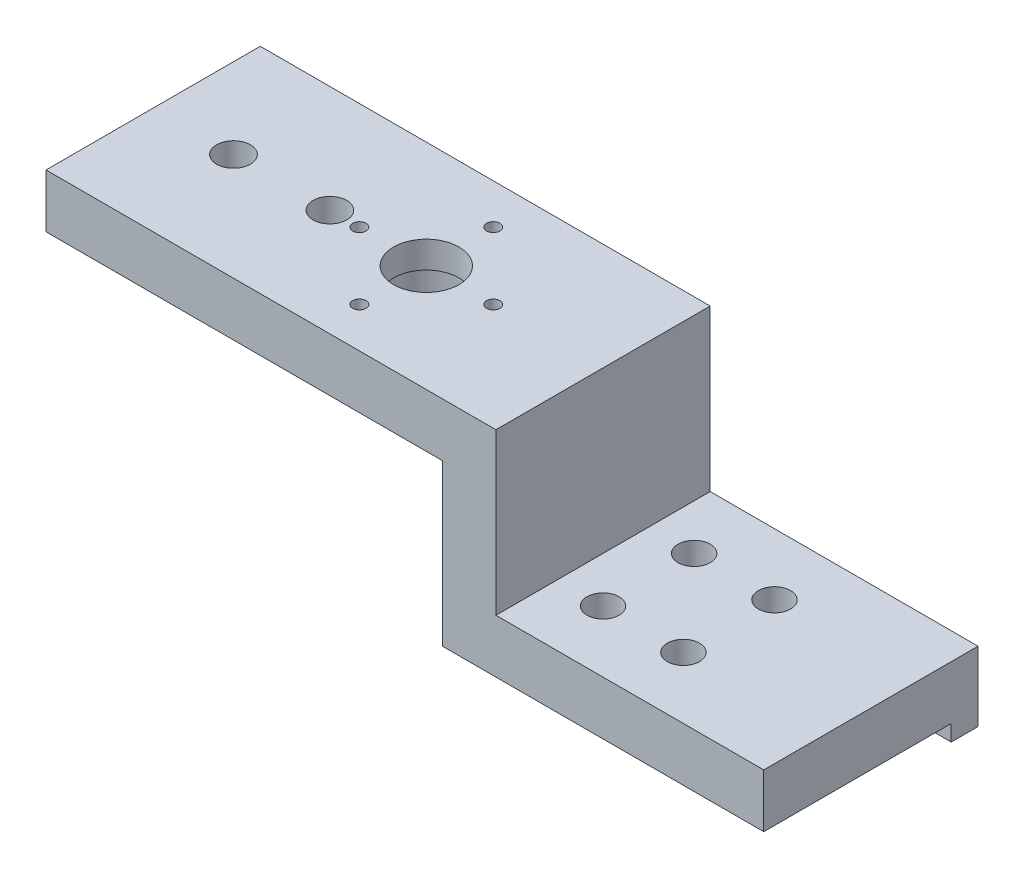
SolidWorks part; units mm, degrees
ref_plane "Front Plane" through (0, 0, 0) normal (0, 0, 1) x (1, 0, 0)
ref_plane "Top Plane" through (0, 0, 0) normal (0, 1, 0) x (1, 0, 0)
ref_plane "Right Plane" through (0, 0, 0) normal (1, 0, 0) x (0, 0, -1)
sketch "Sketch1" plane through (0, 0, 0) normal (0, 1, 0) x (1, 0, 0)
  line L1 (-30, -20) -> (30, -20)
  line L2 (-30, -20) -> (-30, 20)
  line L3 (-30, 20) -> (30, 20)
  line L4 (30, -20) -> (30, 20)
  line L5 (0, 20) -> (0, -20) construction
  line L6 (-30, 0) -> (30, 0) construction
  point P0 (0, 0)
  dimension "D1" = 40
  dimension "D2" = 60
extrude "Boss-Extrude1" add sketch "Sketch1" along normal blind 10 contours L3 L4 L1 L2
sketch "Sketch2" plane through (0, 10, 0) normal (0, 1, 0) x (1, 0, 0)
  line L1 (-20, -20) -> (-30, -20)
  line L2 (-20, -20) -> (-20, 20)
  line L3 (-20, 20) -> (-30, 20)
  line L4 (-30, -20) -> (-30, 20)
  line L5 (-25, 20) -> (-25, -20) construction
  line L6 (-20, 0) -> (-30, 0) construction
  point P0 (-25, 0)
  dimension "D1" = 10
extrude "Boss-Extrude2" add sketch "Sketch2" along normal blind 30
sketch "Sketch3" plane through (-30, 0, 0) normal (-1, 0, 0) x (0, 0, 1)
  line L0 (-20, 40) -> (-20, 0) construction
  line L1 (-20, 30) -> (20, 30)
  line L2 (-20, 30) -> (-20, 40)
  line L3 (-20, 40) -> (20, 40)
  line L4 (20, 30) -> (20, 40)
  line L5 (0, 40) -> (0, 30) construction
  line L6 (-20, 35) -> (20, 35) construction
  point P0 (0, 35)
  dimension "D1" = 10
extrude "Boss-Extrude3" add sketch "Sketch3" along normal blind 74
sketch "Sketch4" plane through (0, 30, 0) normal (0, -1, 0) x (1, 0, 0)
  line L0 (-30, -20) -> (-30, 20) construction
  circle A0 centre (-53, 0) radius 6.1
  circle A1 centre (-71, 0) radius 3.15
  circle A2 centre (-89, 0) radius 3.15
  dimension "D4" = 6.3
  dimension "D5" = 6.3
  dimension "D6" = 12.2
  dimension "D1" = 23
  dimension "D2" = 18
  dimension "D3" = 18
extrude "Cut-Extrude1" cut sketch "Sketch4" against normal blind 74
sketch "Sketch5" plane through (0, 0, 0) normal (0, -1, 0) x (1, 0, 0)
  line L0 (0, 0) -> (-39.9909, 0) construction
  circle A2 centre (-11.5, 8.5) radius 3
  circle A3 centre (-11.5, -8.5) radius 3
  circle A4 centre (-89, 0) radius 3.15 construction
  circle A5 centre (3.5, 8.5) radius 3
  circle A6 centre (3.5, -8.5) radius 3
  dimension "D2" = 77.5
  dimension "D1" = 6
  dimension "D4" = 6
  dimension "D5" = 6
  dimension "D3" = 17
  dimension "D6" = 15
  dimension "D7" = 15
extrude "Cut-Extrude2" cut sketch "Sketch5" against normal blind 74
sketch "Sketch6" plane through (0, 30, 0) normal (0, -1, 0) x (1, 0, 0)
  circle A0 centre (-89, 0) radius 3.5
  circle A1 centre (-71, 0) radius 3.5
  dimension "D3" = 18
  dimension "D1" = 7
  dimension "D2" = 7
extrude "Cut-Extrude3" cut sketch "Sketch6" against normal blind 3
sketch "Sketch7" plane through (0, 30, 0) normal (0, -1, 0) x (1, 0, 0)
  circle A0 centre (-53, 0) radius 6.5
  circle A1 centre (-71, 0) radius 3.5 construction
  dimension "D1" = 13
  dimension "D2" = 18
extrude "Cut-Extrude4" cut sketch "Sketch7" against normal blind 5
hole_wizard "M3 Tapped Hole1" positions "Sketch8" profile "Sketch9" tap size "M3" standard "DIN" end condition through all
sketch "Sketch8" plane through (0, 40, 0) normal (0, 1, 0) x (1, 0, 0)
  circle A0 centre (-53, 0) radius 6.1 construction
  point P1 (-53, 12.5)
  dimension "D1" = 12.5
cosmetic thread "Hole Thread1" parameters "D2"=3
sketch "Sketch9" plane through (-53, 40, -12.5) normal (1, 0, 0) x (0, 0, 1)
  line L0 (0, 0) -> (0, 40)
  line L1 (0, 40) -> (1.25, 40)
  line L2 (1.25, 40) -> (1.25, 0)
  line L5 (1.25, 0) -> (0, 0)
  line L11 (0, -6.35) -> (0, 107.95) construction
  dimension "Thru Tap Drill Dia." = 2.5
  dimension "Thru Tap Drill Depth" = 40
pattern_circular "CirPattern1" count 4 over 360 about axis through (-53, 40, 0) along (0, 1, 0) of "M3 Tapped Hole1"
cosmetic thread "Hole Thread2" parameters "D2"=3
cosmetic thread "Hole Thread3" parameters "D2"=3
cosmetic thread "Hole Thread4" parameters "D2"=3
sketch "Sketch10" plane through (0, 0, 0) normal (0, -1, 0) x (1, 0, 0)
  line L0 (30, 20) -> (30, -20) construction
  line L1 (-30, -20) -> (30, -20)
  line L2 (-30, -20) -> (-30, -15)
  line L3 (-30, -15) -> (30, -15)
  line L4 (30, -20) -> (30, -15)
  dimension "D1" = 5
extrude "Boss-Extrude4" add sketch "Sketch10" along normal blind 3
equation "\"gap_gearbox\"=30"
equation "\"D1@Boss-Extrude2\"=\"gap_gearbox\""
equation "\"transmission_bearing_d_out\"=6.3"
equation "\"D5@Sketch4\"=\"transmission_bearing_d_out\""
equation "\"transmission_gear_dist\"=18"
equation "\"D2@Sketch4\"=\"transmission_gear_dist\""
equation "\"D3@Sketch6\"=\"transmission_gear_dist\""
